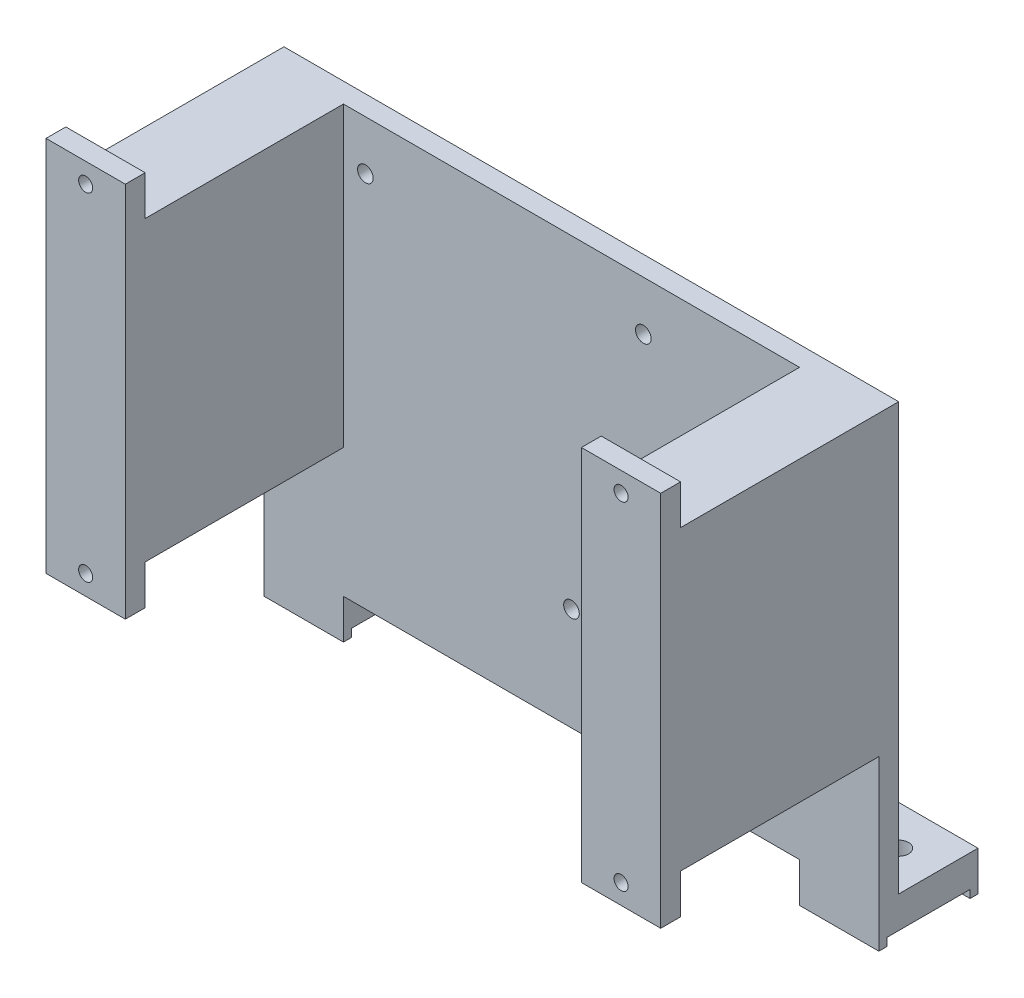
SolidWorks part; units mm, degrees
material "6061 Alloy"
ref_plane "Front Plane" through (0, 0, 0) normal (0, 0, 1) x (1, 0, 0)
ref_plane "Top Plane" through (0, 0, 0) normal (0, 1, 0) x (1, 0, 0)
ref_plane "Right Plane" through (0, 0, 0) normal (1, 0, 0) x (0, 0, -1)
sketch "Sketch1" plane through (0, 0, 0) normal (0, 1, 0) x (1, 0, 0)
  line L1 (-98.425, -41.275) -> (98.425, -41.275)
  line L2 (-98.425, -41.275) -> (-98.425, 41.275)
  line L3 (-98.425, 41.275) -> (98.425, 41.275)
  line L4 (98.425, -41.275) -> (98.425, 41.275)
  line L5 (-98.425, -41.275) -> (98.425, 41.275) construction
  line L6 (-98.425, 41.275) -> (98.425, -41.275) construction
  point P0 (0, 0)
  dimension "D1" = 82.55
  dimension "D2" = 196.85
extrude "Boss-Extrude1" add sketch "Sketch1" along normal blind 95.25
sketch "Sketch3" plane through (0, 95.25, 0) normal (0, 1, 0) x (1, 0, 0)
  line L0 (-98.425, -41.275) -> (98.425, -41.275) construction
  line L1 (-73.025, -41.275) -> (73.025, -41.275)
  line L2 (-73.025, -41.275) -> (-73.025, 34.925)
  line L3 (-73.025, 34.925) -> (73.025, 34.925)
  line L4 (73.025, -41.275) -> (73.025, 34.925)
  line L5 (-98.425, 41.275) -> (-98.425, -41.275) construction
  line L6 (98.425, -41.275) -> (98.425, 41.275) construction
  dimension "D1" = 76.2
  dimension "D2" = 25.4
  dimension "D3" = 25.4
extrude "Cut-Extrude1" cut sketch "Sketch3" against normal through all
sketch "Sketch4" plane through (0, 0, -41.275) normal (0, 0, -1) x (-1, 0, 0)
  line L1 (-98.425, 0) -> (-73.025, 0)
  line L2 (-98.425, 0) -> (-98.425, -53.975)
  line L3 (-98.425, -53.975) -> (-73.025, -53.975)
  line L4 (-73.025, 0) -> (-73.025, -53.975)
  dimension "D1" = 53.975
  dimension "D2" = 25.4
extrude "Boss-Extrude2" add sketch "Sketch4" against normal blind 6.35
sketch "Sketch5" plane through (0, 0, -41.275) normal (0, 0, -1) x (-1, 0, 0)
  line L0 (-73.025, -53.975) -> (-73.025, 0) construction
  line L1 (-98.425, -53.975) -> (-73.025, -53.975)
  line L2 (-98.425, -53.975) -> (-98.425, -41.275)
  line L3 (-98.425, -41.275) -> (-73.025, -41.275)
  line L4 (-73.025, -53.975) -> (-73.025, -41.275)
  dimension "D1" = 12.7
extrude "Boss-Extrude3" add sketch "Sketch5" along normal blind 25.4
sketch "Sketch6" plane through (98.425, 0, 0) normal (1, 0, 0) x (0, 0, -1)
  line L0 (34.925, -53.975) -> (66.675, -53.975) construction
  line L1 (37.465, -53.975) -> (64.135, -53.975)
  line L2 (37.465, -53.975) -> (37.465, -51.435)
  line L3 (37.465, -51.435) -> (64.135, -51.435)
  line L4 (64.135, -53.975) -> (64.135, -51.435)
  line L5 (34.925, 0) -> (34.925, -53.975) construction
  line L6 (66.675, -41.275) -> (66.675, -53.975) construction
  dimension "D1" = 2.54
  dimension "D2" = 2.54
  dimension "D3" = 2.54
extrude "Cut-Extrude2" cut sketch "Sketch6" against normal through all
hole_wizard "1/4 (0.25) Diameter Hole1" positions "Sketch7" profile "Sketch8" hole size "1/4" standard "ANSI Inch" end condition through all
sketch "Sketch7" plane through (0, -41.275, 0) normal (0, 1, 0) x (1, 0, 0)
  line L0 (73.025, 66.675) -> (98.425, 66.675) construction
  line L1 (98.425, 66.675) -> (98.425, 41.275) construction
  point P0 (85.725, 53.975)
  dimension "D1" = 12.7
  dimension "D2" = 12.7
sketch "Sketch8" plane through (85.725, -41.275, -53.975) normal (1, 0, 0) x (0, 0, 1)
  line L0 (0, 0) -> (0, 12.7)
  line L1 (0, 12.7) -> (3.175, 12.7)
  line L2 (3.175, 12.7) -> (3.175, 0)
  line L5 (3.175, 0) -> (0, 0)
  line L11 (0, -6.35) -> (0, 107.95) construction
  dimension "Thru Hole Dia." = 6.35
  dimension "Thru Hole Depth" = 12.7
sketch "Sketch16" plane through (0, 95.25, 0) normal (0, 1, 0) x (1, 0, 0)
  line L0 (98.425, -41.275) -> (98.425, 41.275) construction
  line L1 (-98.425, -41.275) -> (98.425, -41.275)
  line L2 (-98.425, -41.275) -> (-98.425, -34.925)
  line L3 (-98.425, -34.925) -> (98.425, -34.925)
  line L4 (98.425, -41.275) -> (98.425, -34.925)
  dimension "D1" = 6.35
extrude "Cut-Extrude3" cut sketch "Sketch16" against normal through all
sketch "Sketch11" plane through (0, 0, 41.275) normal (0, 0, 1) x (1, 0, 0)
  line L0 (98.425, 0) -> (98.425, -53.975) construction
  line L1 (73.025, 95.25) -> (98.425, 95.25)
  line L2 (73.025, 95.25) -> (73.025, 107.95)
  line L3 (73.025, 107.95) -> (98.425, 107.95)
  line L4 (98.425, 95.25) -> (98.425, 107.95)
  line L5 (73.025, 0) -> (98.425, 0)
  line L6 (73.025, 0) -> (73.025, -12.7)
  line L7 (73.025, -12.7) -> (98.425, -12.7)
  line L8 (98.425, 0) -> (98.425, -12.7)
  dimension "D1" = 25.4
  dimension "D2" = 12.7
  dimension "D3" = 12.7
extrude "Boss-Extrude4" add sketch "Sketch11" against normal blind 6.35 from surface starting at face at (85.725, 47.625, 34.925)
hole_wizard "#8 Clearance Hole1" positions "Sketch12" profile "Sketch13" hole size "#8" standard "ANSI Inch" end condition up to next
sketch "Sketch12" plane through (0, 0, 41.275) normal (0, 0, 1) x (1, 0, 0)
  line L0 (98.425, 107.95) -> (73.025, 107.95) construction
  line L1 (73.025, -12.7) -> (73.025, 107.95) construction
  line L2 (73.025, -12.7) -> (98.425, -12.7) construction
  point P0 (85.725, 101.6)
  point P2 (85.725, -6.35)
  dimension "D1" = 6.35
  dimension "D2" = 12.7
  dimension "D3" = 12.7
  dimension "D4" = 6.35
sketch "Sketch13" plane through (85.725, 101.6, 41.275) normal (1, 0, 0) x (0, -1, 0)
  line L0 (0, 0) -> (0, 12.7)
  line L1 (0, 12.7) -> (2.2479, 12.7)
  line L2 (2.2479, 12.7) -> (2.2479, 0)
  line L5 (2.2479, 0) -> (0, 0)
  line L11 (0, -6.35) -> (0, 107.95) construction
  dimension "Thru Hole Dia." = 4.4958
  dimension "Thru Hole Depth" = 12.7
mirror "Mirror1" about plane through (0, 0, 0) normal (1, 0, 0) of "#8 Clearance Hole1", "Boss-Extrude4", "Boss-Extrude2", "1/4 (0.25) Diameter Hole1", "Cut-Extrude2", "Boss-Extrude3"
sketch "Sketch14" plane through (0, 0, -41.275) normal (0, 0, -1) x (-1, 0, 0)
  line L0 (73.025, -41.275) -> (73.025, 0) construction
  line L1 (-73.025, 0) -> (73.025, 0)
  line L2 (-73.025, 0) -> (-73.025, -41.275)
  line L3 (-73.025, -41.275) -> (73.025, -41.275)
  line L4 (73.025, 0) -> (73.025, -41.275)
  dimension "D1" = 41.275
extrude "Boss-Extrude5" add sketch "Sketch14" against normal blind 6.35
hole_wizard "M6x1.0 Tapped Hole1" positions "Sketch19" profile "Sketch18" tap size "M6x1.0" standard "ANSI Metric" end condition through all
sketch "Sketch19" plane through (0, 0, -41.275) normal (0, 0, -1) x (-1, 0, 0)
  point P0 (-23, 79.4169)
  point P3 (66, 79.4169)
  point P6 (0, -8.3332)
sketch "Sketch18" plane through (23, 79.4169, -41.275) normal (1, 0, 0) x (0, 1, 0)
  line L0 (0, 0) -> (0, 76.2)
  line L1 (0, 76.2) -> (2.5, 76.2)
  line L2 (2.5, 76.2) -> (2.5, 0)
  line L5 (2.5, 0) -> (0, 0)
  line L11 (0, -6.35) -> (0, 107.95) construction
  dimension "Thru Tap Drill Dia." = 5
  dimension "Thru Tap Drill Depth" = 76.2
cosmetic thread "Hole Thread1"
cosmetic thread "Hole Thread2"
cosmetic thread "Hole Thread3"
